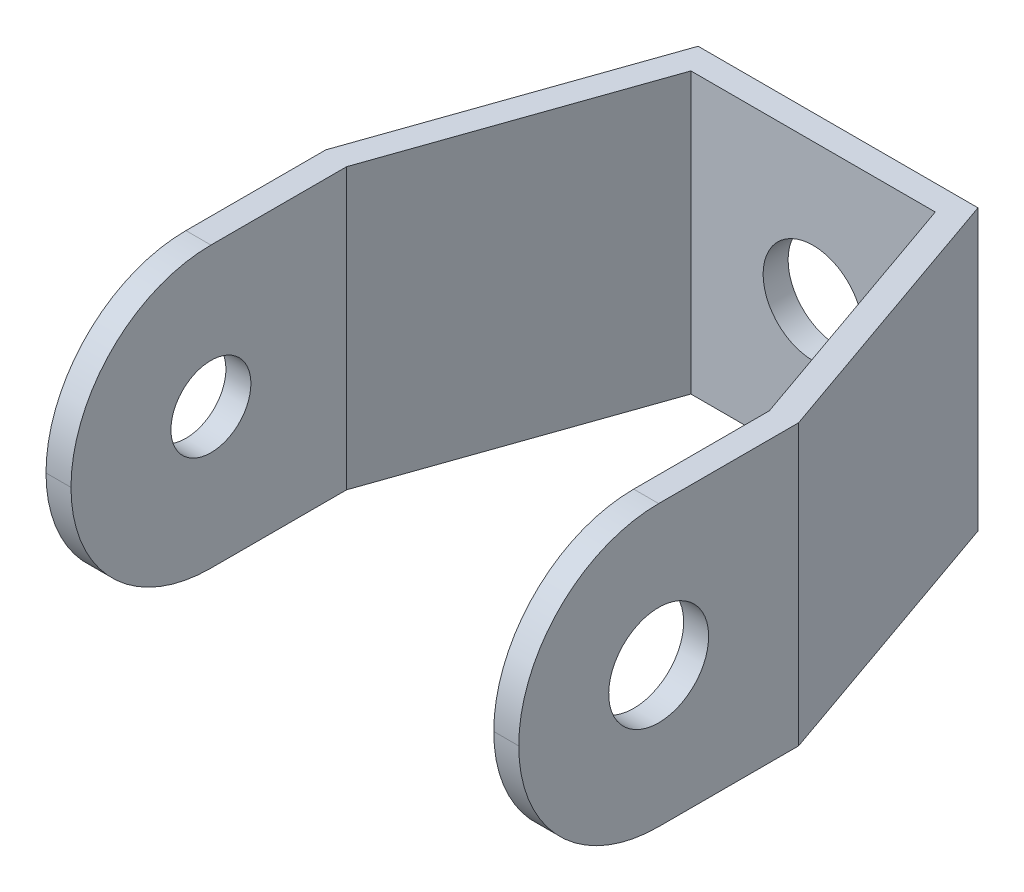
SolidWorks part; units mm, degrees
ref_plane "Plano frontal" through (0, 0, 0) normal (0, 0, 1) x (1, 0, 0)
ref_plane "Plano superior" through (0, 0, 0) normal (0, 1, 0) x (1, 0, 0)
ref_plane "Plano direito" through (0, 0, 0) normal (1, 0, 0) x (0, 0, -1)
sketch "Esboço1" plane through (0, 0, 0) normal (0, 0, 1) x (1, 0, 0)
  line L1 (-23.65, 14) -> (23.65, 14)
  line L2 (-23.65, 14) -> (-23.65, -14)
  line L3 (-23.65, -14) -> (23.65, -14)
  line L4 (23.65, 14) -> (23.65, -14)
  line L5 (-23.65, 14) -> (23.65, -14) construction
  line L6 (-23.65, -14) -> (23.65, 14) construction
  point P0 (0, 0)
  dimension "D1" = 47.3
  dimension "D2" = 28
extrude "Ressalto-extrusão1" add sketch "Esboço1" along normal blind 55.6
sketch "Esboço2" plane through (0, 14, 0) normal (0, 1, 0) x (1, 0, 0)
  line L0 (-23.65, -27.6) -> (-23.65, 0)
  line L1 (23.65, 0) -> (-23.65, 0) construction
  line L2 (-23.65, 0) -> (-14, 0)
  line L3 (-23.65, -55.6) -> (-23.65, 0) construction
  line L4 (-23.65, -27.6) -> (-14, 0)
  line L5 (14, 0) -> (23.65, 0)
  line L6 (23.65, -55.6) -> (23.65, 0) construction
  line L7 (23.65, 0) -> (23.65, -27.6)
  line L8 (14, 0) -> (23.65, -27.6)
extrude "Corte-extrusão1" cut sketch "Esboço2" against normal through all
sketch "Esboço3" plane through (0, 14, 0) normal (0, 1, 0) x (1, 0, 0)
  line L0 (-23.65, -55.6) -> (-23.65, -27.6)
  line L1 (-23.65, -27.6) -> (-14, 0)
  line L2 (-14, 0) -> (14, 0)
  line L3 (14, 0) -> (23.65, -27.6)
  line L4 (23.65, -27.6) -> (23.65, -55.6)
  line L5 (-21.15, -55.6) -> (-21.15, -28.0244)
  line L6 (-21.15, -28.0244) -> (-12.2257, -2.5)
  line L7 (-12.2257, -2.5) -> (12.2257, -2.5)
  line L8 (12.2257, -2.5) -> (21.15, -28.0244)
  line L9 (21.15, -28.0244) -> (21.15, -55.6)
  line L10 (-21.15, -55.6) -> (21.15, -55.6)
  line M5 (-23.65, -55.6) -> (23.65, -55.6)
  dimension "D1" = 2.5
extrude "Corte-extrusão2" cut sketch "Esboço3" against normal through all contours L9 L8 L7 L6 L5 M5 region at (0, 14, 31.0862)
sketch "Esboço4" plane through (23.65, 0, 0) normal (1, 0, 0) x (0, 0, -1)
  line L0 (-27.6, -14) -> (-27.6, 14) construction
  line L2 (-55.6, -14) -> (-27.6, -14) construction
  circle A0 centre (-41.6, 0) radius 5
  point P6 (-43.9728, 10.3231)
  dimension "D3" = 10
  dimension "D1" = 14
  dimension "D2" = 14
extrude "Corte-extrusão3" cut sketch "Esboço4" against normal blind 5.6 and the other way through all
sketch "Esboço5" plane through (-23.65, 0, 0) normal (-1, 0, 0) x (0, 0, 1)
  line L0 (55.6, 14) -> (27.6, 14) construction
  line L1 (27.6, -14) -> (27.6, 14) construction
  circle A0 centre (41.6, 0) radius 4
  dimension "D3" = 8
  dimension "D1" = 14
  dimension "D2" = 14
extrude "Corte-extrusão6" cut sketch "Esboço5" against normal blind 5.6
fillet "Filete1" radius 14 2 edges at (-22.4, -14, 55.6) (-22.4, 14, 55.6)
fillet "Filete2" radius 14 2 edges at (22.4, -14, 55.6) (22.4, 14, 55.6)
sketch "Esboço6" plane through (0, 0, 0) normal (0, 0, -1) x (-1, 0, 0)
  circle A0 centre (0, 0) radius 5
  point P3 (13.7733, 6.6102)
extrude "Corte-extrusão7" cut sketch "Esboço6" against normal blind 5.6
